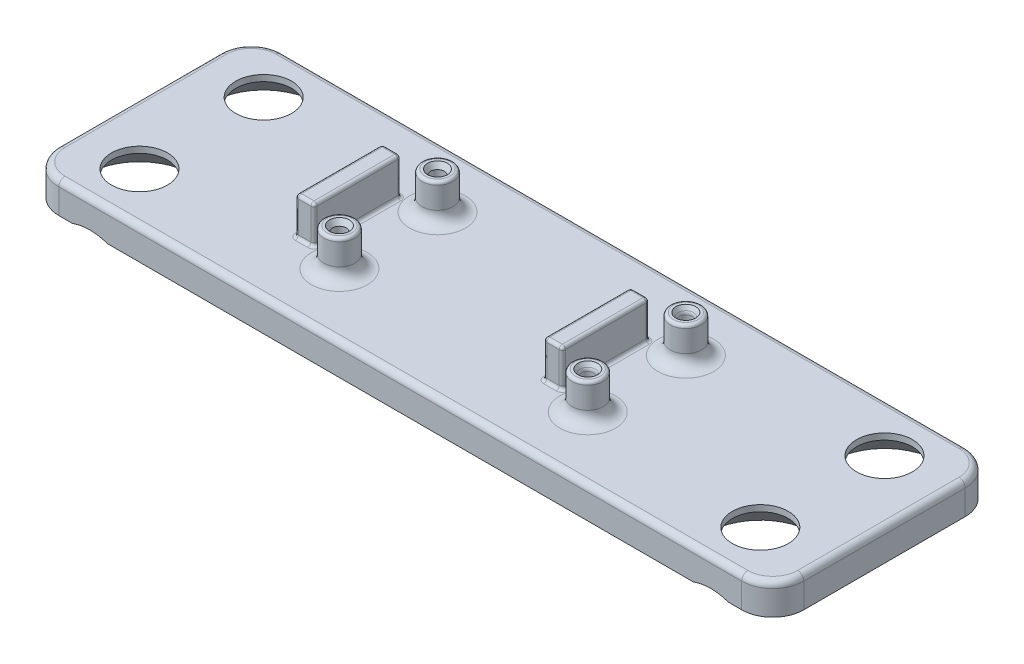
SolidWorks part; units mm, degrees
ref_plane "Спереди" through (0, 0, 0) normal (0, 0, 1) x (1, 0, 0)
ref_plane "Сверху" through (0, 0, 0) normal (0, 1, 0) x (1, 0, 0)
ref_plane "Справа" through (0, 0, 0) normal (1, 0, 0) x (0, 0, -1)
sketch "Эскиз1" plane through (0, 0, 0) normal (0, 1, 0) x (1, 0, 0)
  line L0 (50, -10) -> (-69.2125, -10) construction
  line L1 (-60, -18) -> (60, -18)
  line L2 (-60, -18) -> (-60, 18)
  line L3 (-60, 18) -> (60, 18)
  line L4 (60, -18) -> (60, 18)
  line L5 (0, 18) -> (0, -18) construction
  line L6 (-60, 0) -> (60, 0) construction
  line L7 (50, 10.7603) -> (50, -42.4515) construction
  circle A0 centre (-50, -10) radius 4.5
  circle A1 centre (50, -10) radius 4.5
  circle A2 centre (50, 10) radius 4.5
  circle A3 centre (-50, 10) radius 4.5
  point P0 (0, 0)
  dimension "D3" = 100
  dimension "D4" = 9
  dimension "D6" = 8
  dimension "D7" = 20
  dimension "D8" = 8
  dimension "D1" = 120
  dimension "D2" = 36
  dimension "D5" = 10
extrude "Бобышка-Вытянуть1" add sketch "Эскиз1" along normal blind 5
fillet "Скругление1" radius 5 4 edges at (-60, 2.5, -18) (-60, 2.5, 18) (60, 2.5, -18) (60, 2.5, 18)
sketch "Эскиз2" plane through (0, 5, 0) normal (0, 1, 0) x (1, 0, 0)
  line L0 (20, 8) -> (20, -25.0588) construction
  line L1 (37.0312, 8) -> (-50.4859, 8) construction
  line L2 (55, 18) -> (-55, 18) construction
  line L3 (0, 24.378) -> (0, -24.8256) construction
  line L4 (15, -6.9) -> (15, 7.1)
  line L5 (15, -6.9) -> (12, -6.9)
  line L6 (12, -6.9) -> (12, 7.1)
  line L7 (15, 7.1) -> (12, 7.1)
  line L8 (12, 0.1) -> (15, 0.1) construction
  line L9 (13.5, -6.9) -> (13.5, 7.1) construction
  line L22 (-25, -6.9) -> (-25, 7.1)
  line L23 (-25, -6.9) -> (-28, -6.9)
  line L24 (-28, -6.9) -> (-28, 7.1)
  line L25 (-25, 7.1) -> (-28, 7.1)
  line L26 (-28, 0.1) -> (-25, 0.1) construction
  line L27 (-26.5, -6.9) -> (-26.5, 7.1) construction
  circle A0 centre (20, 8) radius 2.5
  circle A1 centre (20, -7.8) radius 2.5
  circle A2 centre (20, -7.8) radius 1.1
  circle A3 centre (20, 8) radius 1.1
  circle A12 centre (-20, 8) radius 2.5
  circle A13 centre (-20, -7.8) radius 2.5
  circle A14 centre (-20, -7.8) radius 1.1
  circle A15 centre (-20, 8) radius 1.1
  point P12 (13.5, 0.1)
  point P25 (-26.5, 0.1)
  dimension "D1" = 5
  dimension "D2" = 10
  dimension "D3" = 2.2
  dimension "D4" = 15.8
  dimension "D5" = 8
  dimension "D6" = 14
  dimension "D7" = 0.9
  dimension "D8" = 20
  dimension "D9" = 3
  dimension "D10" = 2
extrude "Бобышка-Вытянуть2" add sketch "Эскиз2" along normal blind 6
sketch "Эскиз3" plane through (0, 11, 0) normal (0, 1, 0) x (1, 0, 0)
  circle A0 centre (20, -7.8) radius 1.1
  circle A1 centre (20, 8) radius 1.1
  circle A2 centre (20, 8) radius 1.1 construction
  circle A3 centre (20, -7.8) radius 1.1 construction
extrude "Вырез-Вытянуть1" cut sketch "Эскиз3" against normal blind 8
fillet "Скругление2" radius 2 4 edges at (20, 5, -10.5) (20, 5, 5.3) (-20, 5, -10.5) (-20, 5, 5.3)
fillet "Скругление3" radius 0.5 28 edges at (12, 5, -0.1) (15, 5, -0.1) (15, 8, -7.1) (12, 8, -7.1) (13.5, 5, -7.1) (12, 8, 6.9) (15, 8, 6.9) (13.5, 5, 6.9) (15, 11, -0.1) (13.5, 11, 6.9) (12, 11, -0.1) (13.5, 11, -7.1) (-28, 5, -0.1) (-25, 5, -0.1) (-25, 8, -7.1) (-28, 8, -7.1) (-26.5, 5, -7.1) (-28, 8, 6.9) (-25, 8, 6.9) (-26.5, 5, 6.9) (-25, 11, -0.1) (-26.5, 11, 6.9) (-28, 11, -0.1) (-26.5, 11, -7.1) (-20, 11, 5.3) (-20, 11, -5.5) (20, 11, -5.5) (20, 11, 5.3)
fillet "Скругление4" radius 1 8 edges at (-58.5355, 5, -16.5355) (0, 5, -18) (58.5355, 5, -16.5355) (60, 5, 0) (58.5355, 5, 16.5355) (0, 5, 18) (-58.5355, 5, 16.5355) (-60, 5, 0)
chamfer "Фаска1" distance 4 angle 45 4 edges at (50, 0, 5.5) (-50, 0, 14.5) (-50, 0, -5.5) (50, 0, -14.5)
chamfer "Фаска2" [suppressed] distance 1 angle 45
sketch "Эскиз4" plane through (0, 11, 0) normal (0, 1, 0) x (1, 0, 0)
  line L1 (9.8801, -16.7867) -> (26.379, -16.7867)
  line L2 (9.8801, -16.7867) -> (9.8801, 16.7867)
  line L3 (9.8801, 16.7867) -> (26.379, 16.7867)
  line L4 (26.379, -16.7867) -> (26.379, 16.7867)
  line L5 (18.1296, 16.7867) -> (18.1296, -16.7867) construction
  line L6 (9.8801, 0) -> (26.379, 0) construction
  point P0 (18.1296, 0)
extrude "Вырез-Вытянуть-Тонкостенный1" [suppressed] cut sketch "Эскиз4" against normal blind 20 thin thin type one direction wall 100
chamfer "Фаска3" distance 0.5 angle 60 4 edges at (20, 11, 8.9) (20, 11, -9.1) (-20, 11, 8.9) (-20, 11, -9.1) first distance on face at (20, 11, 5.8) first distance on face at (20, 11, -6) first distance on face at (-20, 11, 5.8) first distance on face at (-20, 11, -6)
fillet "Скругление5" radius 1 2 edges at (20, 10.134, 6.7) (20, 10.134, -6.9)
chamfer "Фаска4" [suppressed] distance 1 angle 45
